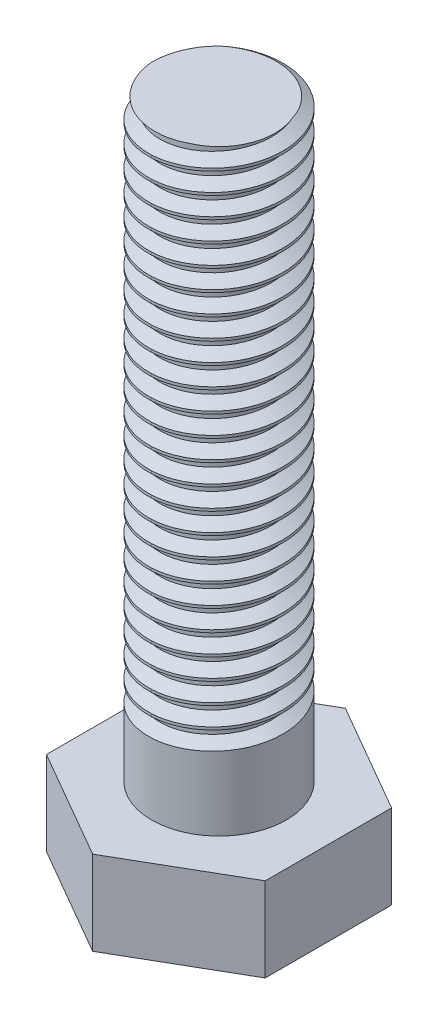
SolidWorks part; units mm, degrees
material "Сталь 45 ГОСТ 1050-88"
ref_plane "Front Plane" through (0, 0, 0) normal (0, 0, 1) x (1, 0, 0)
ref_plane "Top Plane" through (0, 0, 0) normal (0, 1, 0) x (1, 0, 0)
ref_plane "Right Plane" through (0, 0, 0) normal (1, 0, 0) x (0, 0, -1)
sketch "Sketch1" plane through (0, 0, 0) normal (1, 0, 0) x (0, 0, -1)
  line L0 (0, 13.7456) -> (0, -10.8954) construction
  line L1 (-4, 17.5) -> (-4, -17.5)
  line L4 (-4, -17.5) -> (0, -17.5)
  line L5 (-4, 17.5) -> (0, 17.5)
  line L6 (0, 17.5) -> (0, -17.5)
  point P5 (-4, 0)
  point P6 (-4, -17.7938)
  dimension "D2" = 8
  dimension "D3" = 35
revolve "Revolve1" add sketch "Sketch1" angle 360 about L0
thread "Thread1" pitch 1.25 method cut profile "Thread Profile1" start angle 0, offset 5, length 35, pitch 1.25, diameter 8
ref_plane "Plane1" through (-4, 22.5, 0) normal (0, 0, 1) x (-1, 0, 0)
sketch "Thread Profile1" plane through (-4, 22.5, 0) normal (0, 0, 1) x (-1, 0, 0)
  line L0 (0, 0) -> (0, 1.25) construction
  line L11 (0, 0) -> (0, 1.0937)
  line L12 (0, 1.0937) -> (-0.6766, 0.7031)
  line L13 (-0.6766, 0.7031) -> (-0.6766, 0.3906)
  line L15 (-0.6766, 0.3906) -> (0, 0)
  line L17 (-0.6766, 0.5469) -> (0, 0.5469) construction
  point P2 (0, 0)
  dimension "Pitch" = 1.25
  dimension "Profile_Angle" = 60
  dimension "Profile_Land" = 0.3125
  dimension "Profile_Height" = 0.6766
sketch "Sketch7" plane through (0, -17.5, 0) normal (0, -1, 0) x (1, 0, 0)
  line L1 (0, 7.5056) -> (-6.5, 3.7528)
  line L2 (-6.5, 3.7528) -> (-6.5, -3.7528)
  line L3 (-6.5, -3.7528) -> (0, -7.5056)
  line L4 (0, -7.5056) -> (6.5, -3.7528)
  line L5 (6.5, -3.7528) -> (6.5, 3.7528)
  line L6 (6.5, 3.7528) -> (0, 7.5056)
  circle A0 centre (0, 0) radius 6.5 construction
  dimension "D1" = 13
extrude "Boss-Extrude1" add sketch "Sketch7" along normal blind 5
